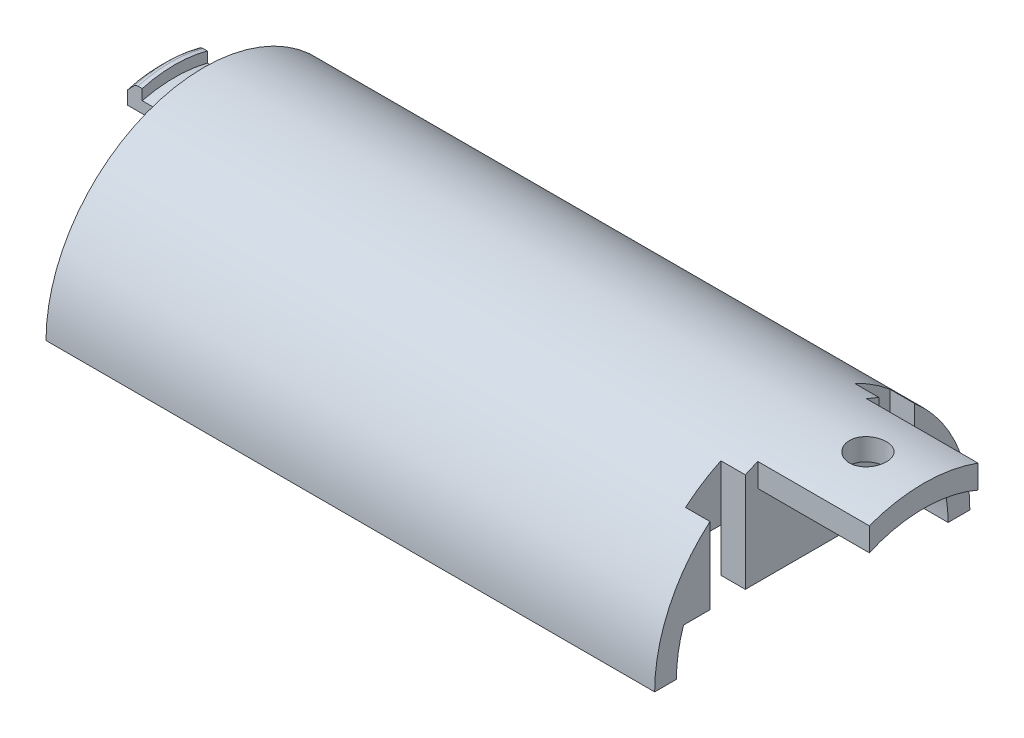
SolidWorks part; units mm, degrees
ref_plane "Alzado" through (0, 0, 0) normal (1, 0, 0) x (0, 1, 0)
ref_plane "Planta" through (0, 0, 0) normal (0, 0, 1) x (0, 1, 0)
ref_plane "Vista lateral" through (0, 0, 0) normal (0, 1, 0) x (-1, 0, 0)
sketch "Croquis2" plane through (0, 0, 0) normal (1, 0, 0) x (0, 1, 0)
  line L0 (0, -14.5) -> (0, 14.5)
  arc A1 (0, -14.5) -> (0, 14.5) centre (0, 0) ccw
  arc A2 (0, -12.5) -> (0, 12.5) centre (0, 0) ccw
  dimension "D1" = 25
  dimension "D2" = 2
extrude "Saliente-Extruir1" add sketch "Croquis2" along normal mid plane 61.5 contours A2 L0 A1 region at (0, 0.3242, -13.5)
ref_plane "Plano1" through (-21.75, 0, 0) normal (1, 0, 0) x (0, 0, -1)
ref_plane "Plano2" through (23, 0, 0) normal (1, 0, 0) x (0, 0, -1)
sketch "Croquis3" plane through (-21.75, 0, 0) normal (1, 0, 0) x (0, 0, -1)
  line L0 (-12.5, 0) -> (-3.75, 0)
  line L1 (3.75, 0) -> (12.5, 0)
  arc A0 (12.5, 0) -> (-12.5, 0) centre (0, 0) ccw construction
  arc A1 (12.5, 0) -> (-12.5, 0) centre (0, 0) ccw
  arc A2 (3.75, 0) -> (-3.75, 0) centre (0, 0) ccw
  dimension "D1" = 7.5
extrude "Saliente-Extruir2" add sketch "Croquis3" against normal blind 2
sketch "Croquis4" plane through (23, 0, 0) normal (1, 0, 0) x (0, 0, -1)
  line L0 (-11.8427, 4) -> (11.8427, 4)
  line L1 (-9.6047, 8) -> (9.6047, 8)
  line L2 (-4.325, 4) -> (-4.325, -8)
  line L3 (-4.325, -8) -> (4.325, -8)
  line L4 (4.325, -8) -> (4.325, 4)
  line L5 (0, 0) -> (0, 4) construction
  line L6 (4.325, -6) -> (-4.325, -6)
  line L8 (14.5, 0) -> (12.5, 0) construction
  arc A0 (12.5, 0) -> (-12.5, 0) centre (0, 0) ccw construction
  arc A1 (11.8427, 4) -> (-11.8427, 4) centre (0, 0) ccw
  circle A2 centre (0, 0) radius 3
  point P7 (0, 12.5)
  dimension "D4" = 6
  dimension "D1" = 4.5
  dimension "D2" = 8.5
  dimension "D3" = 8.65
  dimension "D5" = 8
  dimension "D6" = 2
extrude "Saliente-Extruir3" add sketch "Croquis4" against normal blind 20 contours L1 A1 region at (23, 9.831, 0)
extrude "Saliente-Extruir4" add sketch "Croquis4<4>" along normal blind 3 contours L1 A1 | L0 A1 L1 region at (23, 5.9321, 0) region at (23, 9.831, 0)
sketch "Croquis4<4>" plane through (23, 0, 0) normal (1, 0, 0) x (0, 0, -1) same geometry as "Croquis4"
ref_plane "Plano4" through (0, 13.5, 0) normal (0, 1, 0) x (-1, 0, 0)
sketch "Croquis6" plane through (0, 13.5, 0) normal (0, 1, 0) x (-1, 0, 0)
  line L0 (30.75, -14.5) -> (30.75, 14.5) construction
  line L1 (30.75, -14.5) -> (30.75, 14.5) construction
  line L2 (28.75, -3) -> (30.75, -3)
  line L3 (28.75, -3) -> (28.75, 3)
  line L4 (30.75, -3) -> (30.75, 3)
  line L5 (28.75, 3) -> (30.75, 3)
  line L6 (28.75, -3) -> (30.75, 3) construction
  line L7 (30.75, -3) -> (28.75, 3) construction
  point P3 (29.75, 0)
  point P11 (30.75, 0)
  dimension "D1" = 6
  dimension "D2" = 2
extrude "Saliente-Extruir6" add sketch "Croquis6" against normal blind 2.5
sketch "Croquis7" plane through (-30.75, 0, 0) normal (-1, 0, 0) x (0, -1, 0)
  line L0 (-11, -3) -> (-11, 3) construction
  line L1 (-11, -3) -> (-11, 3) construction
  line L3 (-11, 3) -> (-12.0334, 3)
  line L4 (-11, 3) -> (-11, -3)
  line L5 (-11, -3) -> (-12.0334, -3)
  arc A0 (-12.0334, 3) -> (-12.0334, -3) centre (0, 0) ccw
  arc A1 (-11, 3) -> (-11, -3) centre (0, 0) ccw
  point P2 (-12.4018, 0)
  point P3 (-11.4018, 0)
  line M9 (-12.1347, -3) -> (-11, -3)
  line M10 (-11, -3) -> (-11, 3)
  line M11 (-11, 3) -> (-12.1347, 3)
  dimension "D1" = 1
extrude "Cortar-Extruir1" cut sketch "Croquis7" against normal up to next contours A1 M10 region at (-30.75, 11.1609, 0)
extrude "Saliente-Extruir7" add sketch "Croquis7<4>" along normal blind 4 contours A1 A0 M11 M9 region at (-30.75, 11.7731, 0)
sketch "Croquis7<4>" plane through (-30.75, 0, 0) normal (-1, 0, 0) x (0, -1, 0) same geometry as "Croquis7"
sketch "Croquis8" plane through (-34.75, 0, 0) normal (-1, 0, 0) x (0, -1, 0)
  line L0 (-11, 3) -> (-13, 3)
  line L1 (-13.4018, 0) -> (-11.4018, 0) construction
  line L4 (-13, -3) -> (-11, -3)
  arc A0 (-13, -3) -> (-13, 3) centre (-2, 0) cw
  arc A3 (-11, 3) -> (-11, -3) centre (0, 0) ccw construction
  arc A4 (-11, 3) -> (-11, -3) centre (0, 0) ccw
  point P2 (-13.4018, 0)
  point P9 (-11.4018, 0)
  dimension "D1" = 2
  dimension "D2" = 2
extrude "Saliente-Extruir9" add sketch "Croquis8" against normal blind 1.35
chamfer "Chaflán3" distance 0.75 angle 45 1 edges at (-34.75, 13.4018, 0)
fillet "Redondeo1" radius 0.5 1 edges at (-34, 13.4018, 0)
chamfer "Chaflán4" distance 1 angle 45 1 edges at (-28.75, 12.5, 0)
sketch "Croquis9" plane through (30.75, 0, 0) normal (1, 0, 0) x (0, 1, 0)
  line L1 (4, 11.8427) -> (4, -11.8427)
  line L2 (0, -12.5) -> (0, -14.5)
  line L3 (0, 14.5) -> (0, 12.5)
  line L4 (0, -12.5) -> (0, -14.5)
  line L5 (0, 14.5) -> (0, 12.5)
  line L6 (4, 11.8427) -> (4, -11.8427)
  arc A1 (4, -11.8427) -> (4, 11.8427) centre (0, 0) ccw
  arc A2 (0, -12.5) -> (0, 12.5) centre (0, 0) ccw
  arc A3 (0, -14.5) -> (0, 14.5) centre (0, 0) ccw
  arc A4 (0, -12.5) -> (0, 12.5) centre (0, 0) ccw
  arc A5 (0, -14.5) -> (0, 14.5) centre (0, 0) ccw
  arc A6 (4, -11.8427) -> (4, 11.8427) centre (0, 0) ccw
  arc M5 (0, 12.5) -> (0, -12.5) centre (0, 0) cw
  line M6 (0, -12.5) -> (0, -14.5)
  arc M7 (0, -14.5) -> (0, 14.5) centre (0, 0) ccw
  line M8 (0, 14.5) -> (0, 12.5)
  dimension "D1" = 0
  dimension "D2" = 0
extrude "Cortar-Extruir2" cut sketch "Croquis9" against normal blind 5.5 contours L6 M5 | M8 M5 M6 M7 region at (30.75, 7.5239, 0) region at (30.75, 2.0794, 12.6545)
sketch "Croquis10" plane through (25.25, 0, 0) normal (1, 0, 0) x (0, 1, 0)
  line L0 (11.4564, 5) -> (13.6107, 5)
  line L1 (11.4564, -5) -> (13.6107, -5)
  line L2 (14.5, 0) -> (12.5, 0) construction
  arc A0 (0, -12.5) -> (0, 12.5) centre (0, 0) ccw construction
  arc A1 (11.4564, -5) -> (11.4564, 5) centre (0, 0) ccw
  arc A4 (0, -14.5) -> (0, 14.5) centre (0, 0) ccw construction
  arc A5 (13.6107, -5) -> (13.6107, 5) centre (0, 0) ccw
  dimension "D1" = 5
extrude "Saliente-Extruir10" add sketch "Croquis10" along normal blind 10.25
ref_plane "Plano5" through (0, 14.5, 0) normal (0, 1, 0) x (-1, 0, 0)
sketch "Croquis11" plane through (0, 14.5, 0) normal (0, 1, 0) x (-1, 0, 0)
  line L0 (-35.5, 5) -> (-25.25, -5) construction
  circle A0 centre (-30.375, 0) radius 1.7
  point P4 (-30.375, 0)
  dimension "D1" = 3.4
extrude "Cortar-Extruir3" cut sketch "Croquis11" against normal up to next
sketch "Croquis14" plane through (0, 4, 0) normal (0, -1, 0) x (1, 0, 0)
  line L0 (25.25, 11.8427) -> (25.25, -11.8427) construction
  line L1 (25.25, 9.41) -> (23, 9.41)
  line L2 (25.25, 9.41) -> (25.25, 6.16)
  line L3 (25.25, 6.16) -> (23, 6.16)
  line L4 (23, 9.41) -> (23, 6.16)
  line L5 (23, 11.8427) -> (23, -11.8427) construction
  line L6 (0, 0) -> (10.089, 0) construction
  line L7 (25.25, -9.41) -> (23, -9.41)
  line L8 (25.25, -9.41) -> (25.25, -6.16)
  line L9 (25.25, -6.16) -> (23, -6.16)
  line L10 (23, -9.41) -> (23, -6.16)
  point P15 (25.25, 7.785)
  point P16 (25.25, -7.785)
  dimension "D1" = 15.57
  dimension "D2" = 3.25
extrude "Cortar-Extruir6" cut sketch "Croquis14" against normal through all
equation "\"D2@Croquis8\"=\"D1@Croquis8\""
